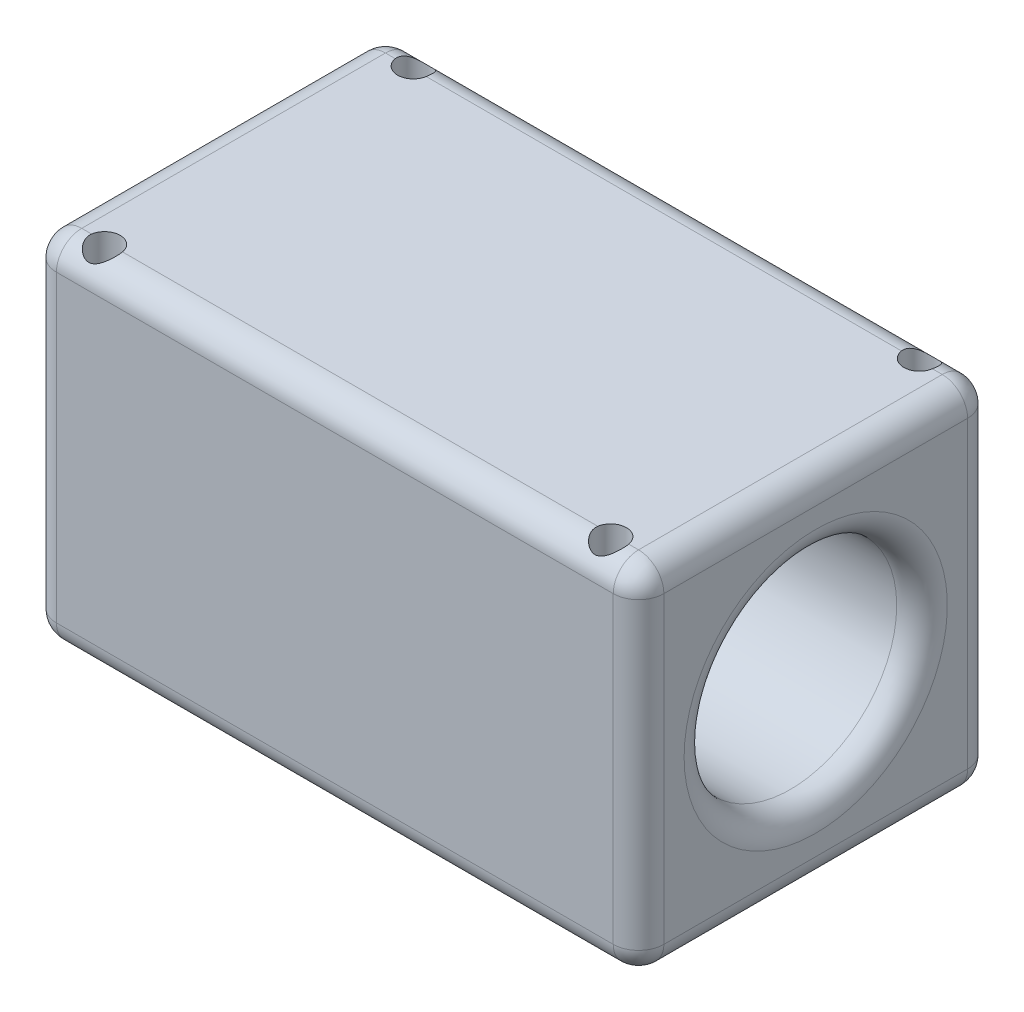
SolidWorks part; units mm, degrees
ref_plane "Front Plane" through (0, 0, 0) normal (0, 0, 1) x (1, 0, 0)
ref_plane "Top Plane" through (0, 0, 0) normal (0, 1, 0) x (1, 0, 0)
ref_plane "Right Plane" through (0, 0, 0) normal (1, 0, 0) x (0, 0, -1)
sketch "Sketch1" plane through (0, 0, 0) normal (0, 1, 0) x (1, 0, 0)
  line L1 (-30, -17.5) -> (30, -17.5)
  line L2 (-30, -17.5) -> (-30, 17.5)
  line L3 (-30, 17.5) -> (30, 17.5)
  line L4 (30, -17.5) -> (30, 17.5)
  line L5 (-30, -17.5) -> (30, 17.5) construction
  line L6 (-30, 17.5) -> (30, -17.5) construction
  point P0 (0, 0)
  dimension "D1" = 60
  dimension "D2" = 35
extrude "Boss-Extrude1" add sketch "Sketch1" along normal blind 35
sketch "Sketch2" plane through (-30, 0, 0) normal (-1, 0, 0) x (0, 0, 1)
  circle A0 centre (0, 17.5) radius 10.5
  dimension "D1" = 21
extrude "Cut-Extrude1" cut sketch "Sketch2" against normal up to surface (60 mm away) up to face at (30, 17.5, 0)
sketch "Sketch3" plane through (0, 35, 0) normal (0, 1, 0) x (1, 0, 0)
  circle A0 centre (-25, 15.25) radius 1.55
  circle A1 centre (25, 15.25) radius 1.55
  circle A3 centre (-25, -15.25) radius 1.55
  circle A4 centre (25, -15.25) radius 1.55
  dimension "D1" = 50
  dimension "D2" = 30.5
  dimension "D3" = 3.1
  dimension "D4" = 3.1
  dimension "D5" = 3.1
  dimension "D6" = 3.1
  dimension "D7" = 15.25
  dimension "D8" = 25
extrude "Cut-Extrude2" cut sketch "Sketch3" against normal up to surface (35 mm away) up to face at (0, 0, 0)
fillet "Fillet1" radius 2.5 14 edges at (30, 35, 0) (0, 35, 17.5) (30, 17.5, 17.5) (0, 0, 17.5) (30, 0, 0) (30, 17.5, -17.5) (0, 35, -17.5) (0, 0, -17.5) (-30, 17.5, -17.5) (-30, 35, 0) (-30, 17.5, 17.5) (-30, 0, 0) (-30, 17.5, 10.5) (30, 17.5, 10.5)
